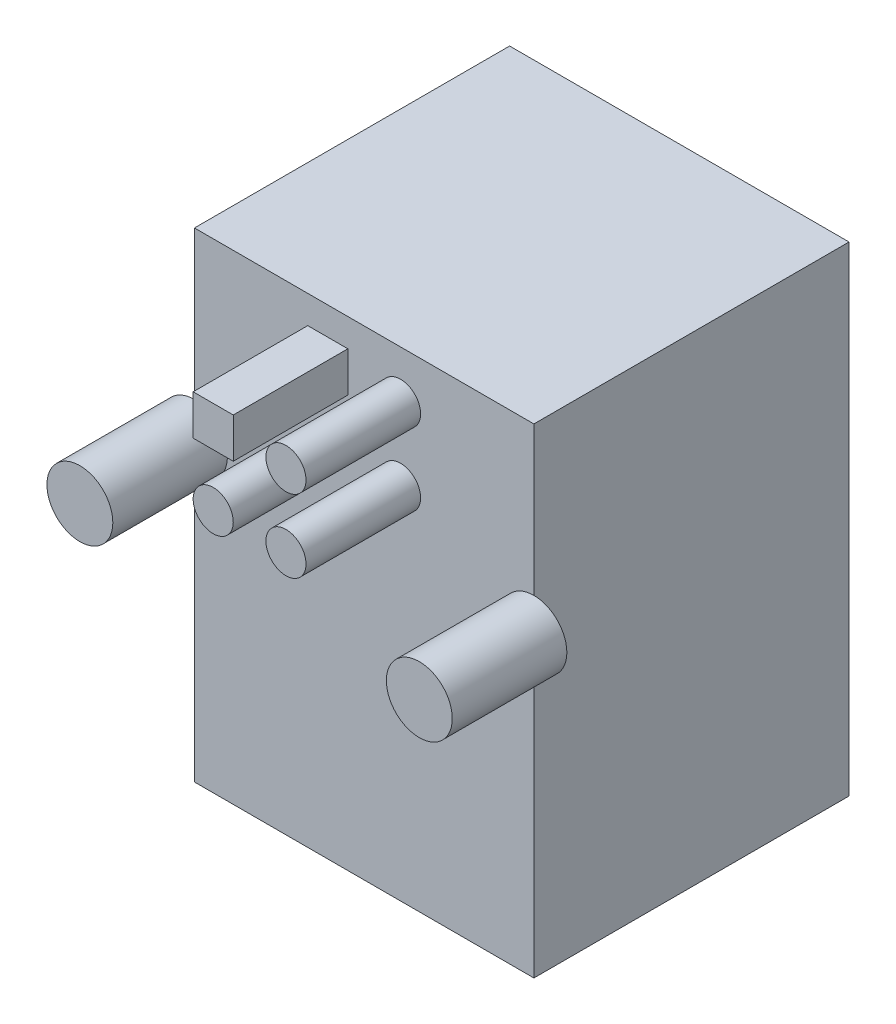
SolidWorks part; units mm, degrees
ref_plane "Front Plane" through (0, 0, 0) normal (0, 0, 1) x (1, 0, 0)
ref_plane "Top Plane" through (0, 0, 0) normal (0, 1, 0) x (1, 0, 0)
ref_plane "Right Plane" through (0, 0, 0) normal (1, 0, 0) x (0, 0, -1)
sketch "Sketch1" plane through (0, 0, 0) normal (0, 0, 1) x (1, 0, 0)
  line L0 (0, -9.2118) -> (0, 9.2118) construction
  line L1 (7.7812, 0) -> (-7.7812, 0) construction
  line L4 (-5.9238, 0) -> (5.9238, 0) construction
  line L5 (5.9238, 6.3335) -> (-5.9238, -10.4153) construction
  line L6 (0, 6.3335) -> (0, -10.4153) construction
  line L7 (1.27, 4.6575) -> (1.27, 2.1175) construction
  line L8 (5.9238, -10.4153) -> (5.9238, 6.3335)
  line L9 (5.9238, 6.3335) -> (-5.9238, 6.3335)
  line L10 (-5.9238, 6.3335) -> (-5.9238, -10.4153)
  line L11 (-5.9238, -10.4153) -> (5.9238, -10.4153)
  line L12 (-1.97, 3.9575) -> (-0.57, 3.9575)
  line L13 (-0.57, 3.9575) -> (-0.57, 5.3575)
  line L14 (-0.57, 5.3575) -> (-1.97, 5.3575)
  line L15 (-1.97, 5.3575) -> (-1.97, 3.9575)
  line L16 (1.27, 2.1175) -> (-1.27, 2.1175) construction
  line L17 (-1.27, 2.1175) -> (-1.27, 4.6575) construction
  line L18 (-1.27, 4.6575) -> (1.27, 4.6575) construction
  line L19 (1.27, 4.6575) -> (-1.27, 2.1175) construction
  line L20 (-1.97, 3.9575) -> (-0.57, 5.3575) construction
  circle A5 centre (5.9238, 0) radius 1.15
  circle A6 centre (1.27, 4.6575) radius 0.7
  circle A7 centre (1.27, 2.1175) radius 0.7
  circle A8 centre (-1.27, 2.1175) radius 0.7
  circle A9 centre (-5.9238, 0) radius 1.15
  point P9 (-1.27, 4.6575)
  point P13 (0, 3.3875)
  dimension "D3" = 2.3
  dimension "D4" = 1.4
  dimension "D6" = 10.4153
  dimension "D1" = 16.7487
  dimension "D2" = 11.8476
  dimension "D5" = 1.4
  dimension "D7" = 2.54
  dimension "D8" = 2.54
  dimension "D9" = 2.1175
extrude "Boss-Extrude1" add sketch "Sketch1" against normal blind 11 contours L10 L11 L8 L9
extrude "Boss-Extrude2" add sketch "Sketch1<3>" along normal blind 4 contours L8 A5 | A8 | A6 | L14 L15 L12 L13 | L8 A5 | A9 | A7 region at (5.4357, 0, 0) region at (6.4119, 0, 0) region at (-1.27, 4.6575, 0) region at (1.27, 4.6575, 0) region at (-1.27, 2.1175, 0)
sketch "Sketch1<3>" plane through (0, 0, 0) normal (0, 0, 1) x (1, 0, 0) same geometry as "Sketch1"
